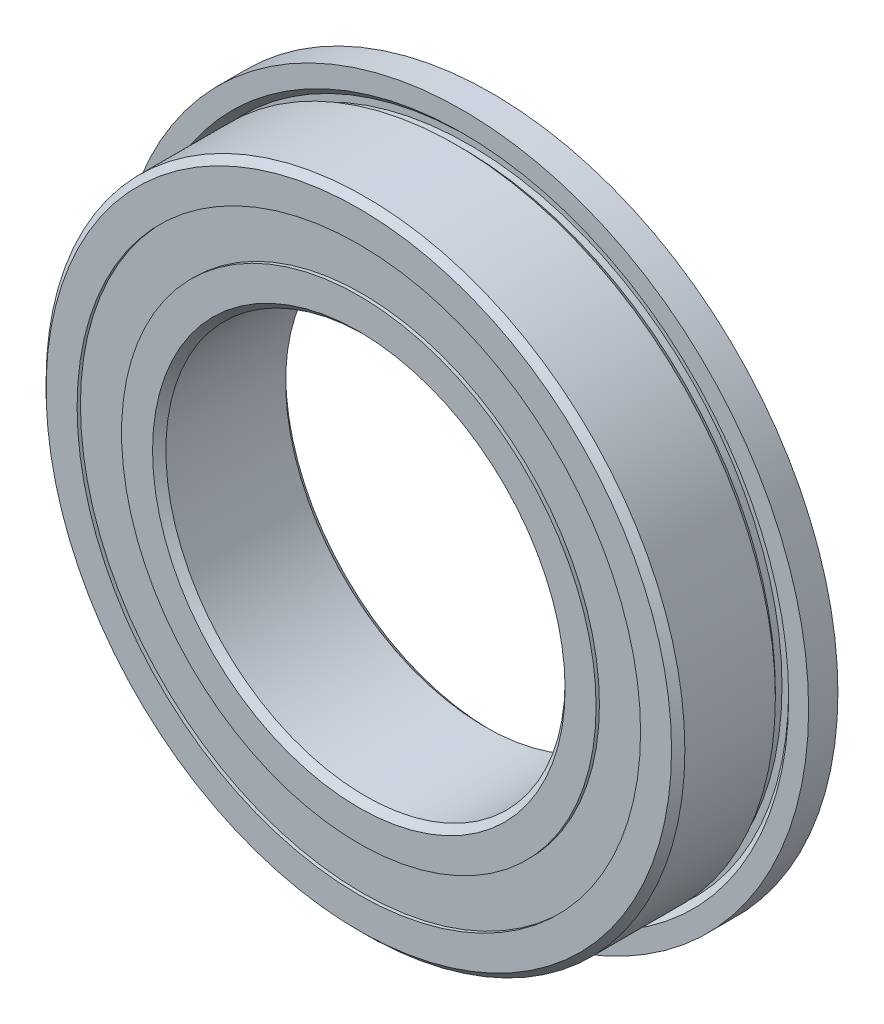
SolidWorks part; units mm, degrees
ref_plane "Front Plane" through (0, 0, 0) normal (0, 0, 1) x (1, 0, 0)
ref_plane "Top Plane" through (0, 0, 0) normal (0, 1, 0) x (1, 0, 0)
ref_plane "Right Plane" through (0, 0, 0) normal (1, 0, 0) x (0, 0, -1)
sketch "Sketch1" plane through (0, 0, 0) normal (1, 0, 0) x (0, 0, -1)
  line L0 (-2.5, 0) -> (2.5, 0) construction
  line L1 (0, 12) -> (0, -12) construction
  line L2 (2.25, 12) -> (-2.25, 12) construction
  line L3 (-2.25, 12) -> (-2.5, 11.75)
  line L4 (-2.5, 11.75) -> (-2.5, 10.5852)
  line L5 (-2.5, 10.5852) -> (-1.1111, 10.5852)
  line L6 (2.5, 10.5852) -> (1.1111, 10.5852)
  line L7 (2.5, 11.75) -> (2.5, 10.5852)
  line L8 (2.25, 12) -> (2.5, 11.75) construction
  line L9 (0, 12) -> (0, 9.75) construction
  line L10 (0, 9.75) -> (0, 7.5) construction
  line L11 (1.4, 0) -> (1.4, 12) construction
  line L12 (2.5, 11.75) -> (2.5, 13)
  line L13 (2.5, 13) -> (1.4, 13)
  line L14 (1.4, 13) -> (1.4, 12.25)
  line L15 (1.4, 12.25) -> (1.65, 12)
  line L16 (1.65, 12) -> (1.65, 11.75)
  line L17 (1.65, 11.75) -> (1.4, 11.75)
  line L18 (1.4, 11.75) -> (1.15, 12)
  line L19 (-2.25, 12) -> (1.15, 12)
  line L20 (2.5, 13) -> (2.5, -13) construction
  line L21 (1.4, 12) -> (1.4, 12.25) construction
  line L22 (1.4, 12) -> (1.15, 12) construction
  arc A0 (-1.1111, 10.5852) -> (1.1111, 10.5852) centre (0, 9.75) cw
  point P14 (0, 7.5)
  point P15 (1.4, 0)
  point P25 (2.5, 0)
  dimension "Width" = 5
  dimension "OD" = 24
  dimension "D1" = 45
  dimension "D2" = 0.25
  dimension "ID" = 15
  dimension "D3" = 2.2222
  dimension "D4" = 0.8352
  dimension "Th" = 1.1
  dimension "Flange OD" = 26
revolve "Revolve1" add sketch "Sketch1" angle 360 about L0
sketch "Sketch3" plane through (0, 0, 0) normal (1, 0, 0) x (0, 0, -1)
  line L0 (-2.5, 8.9148) -> (-1.1111, 8.9148)
  line L1 (0, 12) -> (0, -12) construction
  line L2 (-2.5, 11.75) -> (-2.5, 10.5852) construction
  line L3 (-2.5, 8.9148) -> (-2.5, 7.75)
  line L4 (-2.25, 12) -> (-2.5, 11.75) construction
  line L5 (-2.5, 7.75) -> (-2.25, 7.5)
  line L6 (-2.25, 7.5) -> (2.25, 7.5)
  line L8 (2.25, 7.5) -> (2.5, 7.75)
  line L10 (2.5, 7.75) -> (2.5, 8.9148)
  line L11 (2.5, 8.9148) -> (1.1111, 8.9148)
  line L13 (2.25, 12) -> (2.5, 11.75) construction
  arc A0 (1.1111, 10.5852) -> (-1.1111, 10.5852) centre (0, 9.75) ccw construction
  arc A1 (1.1111, 8.9148) -> (-1.1111, 8.9148) centre (0, 9.75) cw
revolve "Revolve3" add sketch "Sketch3" angle 360 about L0
sketch "Sketch6" plane through (0, 0, 0) normal (1, 0, 0) x (0, 0, -1)
  line L1 (-0.1392, 10.1676) -> (0.1392, 10.1676)
  line L2 (-0.1392, 10.1676) -> (-0.1392, 9.3324)
  line L3 (-0.1392, 9.3324) -> (0.1392, 9.3324)
  line L4 (0.1392, 10.1676) -> (0.1392, 9.3324)
  line L5 (-0.1392, 10.1676) -> (0.1392, 9.3324) construction
  line L6 (-0.1392, 9.3324) -> (0.1392, 10.1676) construction
  point P4 (0, 9.75)
  dimension "D1" = 0.8352
  dimension "D2" = 0.2784
revolve "Revolve6" add sketch "Sketch6" angle 360 about L0
sketch "Sketch4" plane through (0, 0, 0) normal (1, 0, 0) x (0, 0, -1)
  line L0 (-1.39, 9.75) -> (1.39, 9.75)
  arc A2 (-1.39, 9.75) -> (1.39, 9.75) centre (0, 9.75) cw
  arc A3 (1.1111, 10.5852) -> (-1.1111, 10.5852) centre (0, 9.75) ccw construction
revolve "Revolve4" add sketch "Sketch4" angle 360 about L0
ref_axis "Axis1" through (0, 0, -2.5) along (0, 0, 1)
pattern_circular "CirPattern1" count 14 every 25.714 about axis through (0, 0, -2.5) along (0, 0, 1) of bodies 104
sketch "Sketch5" plane through (0, 0, 0) normal (1, 0, 0) x (0, 0, -1)
  line L0 (-2.5, 10.5852) -> (-1.1111, 10.5852) construction
  line L1 (-2.375, 10.5852) -> (-1.39, 10.5852)
  line L2 (-2.375, 10.5852) -> (-2.375, 8.9148)
  line L3 (-2.375, 8.9148) -> (-1.39, 8.9148)
  line L4 (-1.39, 10.5852) -> (-1.39, 8.9148)
  line L5 (-2.5, 8.9148) -> (-1.1111, 8.9148) construction
  line L6 (2.5, 10.5852) -> (1.1111, 10.5852) construction
  line L7 (2.375, 10.5852) -> (1.39, 10.5852)
  line L8 (2.375, 10.5852) -> (2.375, 8.9148)
  line L9 (2.375, 8.9148) -> (1.39, 8.9148)
  line L10 (1.39, 10.5852) -> (1.39, 8.9148)
  line L11 (2.5, 8.9148) -> (1.1111, 8.9148) construction
  line L12 (-2.25, 12) -> (-2.5, 11.75) construction
  point P18 (-2.375, 11.875)
revolve "Revolve5" add sketch "Sketch5" angle 360 about L0
ref_axis "Center Axis 1" through (0, 0, -2.25) along (0, 0, 1)
ref_plane "Contact Plane 1" through (0, 0, -2.5) normal (0, 0, -1) x (-1, 0, 0)
ref_plane "Contact Plane 2" through (0, 0, -1.4) normal (0, 0, 1) x (1, 0, 0)
equation "\"D2@Sketch1\" = \"Width@Sketch1\"*.05"
equation "\"D3@Sketch1\" = \"Width@Sketch1\"/2.25"
equation "\"D4@Sketch1\" = (((\"OD@Sketch1\"-\"Width@Sketch1\")/2)/3.25)/3.5"
equation "\"D2@CirPattern1\" = 360/\"Balls@CirPattern1\""
equation "\"D1@Sketch6\"=\"D4@Sketch1\""
equation "\"D2@Sketch6\"=\"D1@Sketch6\"/3"
